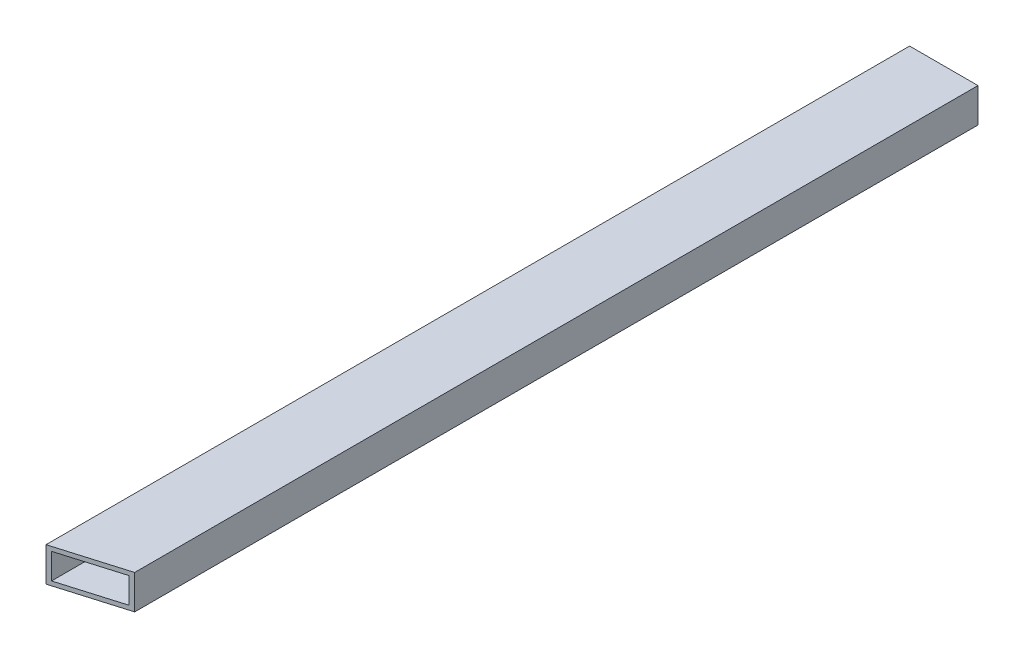
SolidWorks part; units mm, degrees
material "1060 Alloy"
ref_plane "Front Plane" through (0, 0, 0) normal (0, 0, 1) x (1, 0, 0)
ref_plane "Top Plane" through (0, 0, 0) normal (0, 1, 0) x (1, 0, 0)
ref_plane "Right Plane" through (0, 0, 0) normal (1, 0, 0) x (0, 0, -1)
sketch "Sketch1" plane through (0, 0, 0) normal (0, 0, 1) x (1, 0, 0)
  line L0 (-22.225, 9.525) -> (22.225, 9.525)
  line L2 (-25.4, 12.7) -> (25.4, 12.7)
  line L3 (-25.4, 12.7) -> (-25.4, -12.7)
  line L4 (-25.4, -12.7) -> (25.4, -12.7)
  line L5 (25.4, 12.7) -> (25.4, -12.7)
  line L10 (22.225, 9.525) -> (22.225, -9.525)
  line L11 (-22.225, -9.525) -> (22.225, -9.525)
  line L12 (-22.225, 9.525) -> (-22.225, -9.525)
  point P12 (0, 12.7)
  point P14 (25.4, 0)
  dimension "Wall Thickness" = 3.175
  dimension "Outside Width" = 50.8
  dimension "Outside Height" = 25.4
  dimension "Inside Height" = 19.05
  dimension "Inside Width" = 44.45
sketch "Sketch2" plane through (0, 0, 0) normal (1, 0, 0) x (0, 0, -1)
  line L0 (320.675, 0) -> (-320.675, 0)
  point P4 (0, 0)
  point P7 (-320.675, 0)
  point P10 (320.675, 0)
  dimension "Length" = 641.35
sketch "Sketch3" plane through (0, 0, 0) normal (0, 0, 1) x (1, 0, 0)
  line L21 (25.4, 12.7) -> (-25.4, 12.7)
  line L22 (25.4, -12.7) -> (25.4, 12.7)
  line L23 (-25.4, -12.7) -> (25.4, -12.7)
  line L24 (-25.4, 12.7) -> (-25.4, -12.7)
  line L25 (25.4, 12.7) -> (-25.4, 12.7)
  line L26 (25.4, -12.7) -> (25.4, 12.7)
  line L27 (-25.4, -12.7) -> (25.4, -12.7)
  line L28 (-25.4, 12.7) -> (-25.4, -12.7)
  line L29 (22.225, 9.525) -> (-22.225, 9.525)
  line L30 (22.225, -9.525) -> (22.225, 9.525)
  line L31 (-22.225, -9.525) -> (22.225, -9.525)
  line L32 (-22.225, 9.525) -> (-22.225, -9.525)
  line L33 (22.225, 9.525) -> (-22.225, 9.525)
  line L34 (22.225, -9.525) -> (22.225, 9.525)
  line L35 (-22.225, -9.525) -> (22.225, -9.525)
  line L36 (-22.225, 9.525) -> (-22.225, -9.525)
  dimension "D1" = 0
  dimension "D2" = 0
extrude "Boss-Extrude1" add sketch "Sketch3" along normal up to vertex (320.675 mm away) and the other way up to vertex (320.675 mm away) up to point (0, 0, 320.675) other way up to point (0, 0, -320.675)
sketch "Drawing Reference" plane through (0, 0, 0) normal (1, 0, 0) x (0, 0, -1)
  line L0 (-320.675, 0) -> (320.675, 0) construction
  line L1 (0, -12.7) -> (0, 12.7) construction
  line L2 (-320.675, -12.7) -> (320.675, -12.7) construction
  line L5 (-320.675, 12.7) -> (320.675, 12.7) construction
  point P7 (-284.099, 0)
  point P8 (284.099, 0)
  dimension "D1" = 36.576
sketch "Sketch4" plane through (0, 12.7, 0) normal (0, 1, 0) x (1, 0, 0)
  line L0 (-25.4, -320.675) -> (25.4, -305.6274)
  line L1 (25.4, -320.675) -> (25.4, 320.675) construction
  line L2 (25.4, -320.675) -> (-25.4, -320.675)
  dimension "D1" = 16.5
extrude "Cut-Extrude1" cut sketch "Sketch4" against normal through all and the other way through all flip side to cut
equation "\"D1@Drawing Reference\"=\"Outside Width@Sketch1\" * 0.72"
